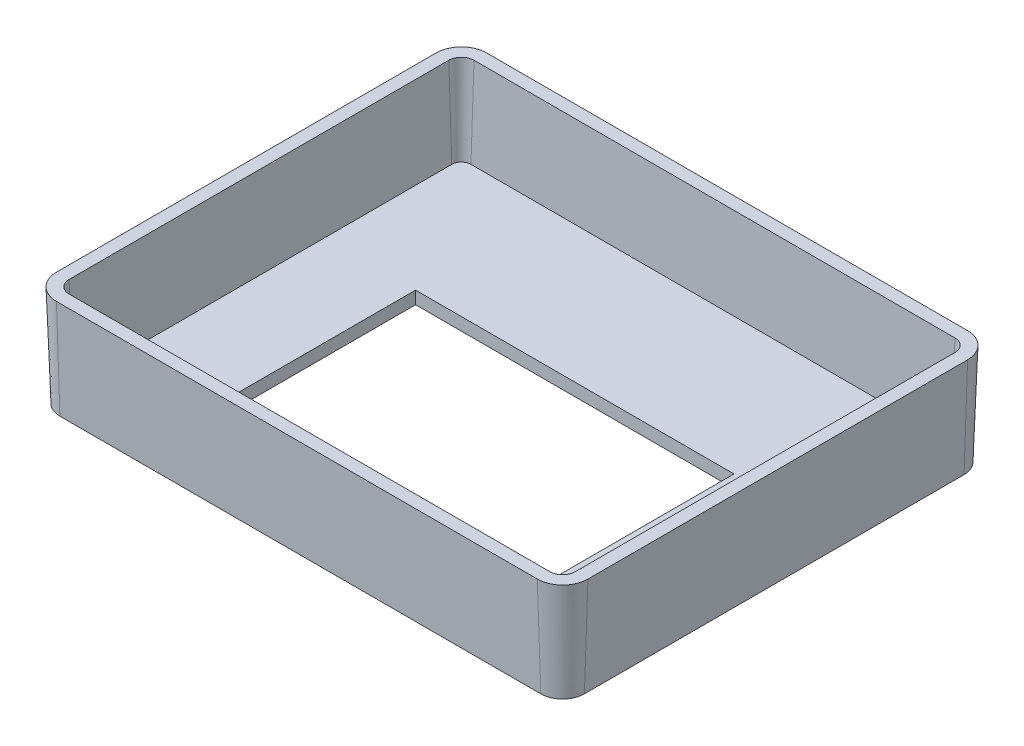
SolidWorks part; units mm, degrees
ref_plane "Front Plane" through (0, 0, 0) normal (0, 0, 1) x (1, 0, 0)
ref_plane "Top Plane" through (0, 0, 0) normal (0, 1, 0) x (1, 0, 0)
ref_plane "Right Plane" through (0, 0, 0) normal (1, 0, 0) x (0, 0, -1)
sketch "Sketch1" plane through (0, 0, 0) normal (0, 1, 0) x (1, 0, 0)
  line L1 (-9.5, -8.5) -> (9.5, -8.5)
  line L2 (-10.5, -7.5) -> (-10.5, 7.5)
  line L3 (-9.5, 8.5) -> (9.5, 8.5)
  line L4 (10.5, -7.5) -> (10.5, 7.5)
  line L5 (-10.5, -8.5) -> (10.5, 8.5) construction
  line L6 (-10.5, 8.5) -> (10.5, -8.5) construction
  arc A0 (-10.5, 7.5) -> (-9.5, 8.5) centre (-9.5, 7.5) cw
  arc A1 (10.5, 7.5) -> (9.5, 8.5) centre (9.5, 7.5) ccw
  arc A2 (10.5, -7.5) -> (9.5, -8.5) centre (9.5, -7.5) cw
  arc A3 (-9.5, -8.5) -> (-10.5, -7.5) centre (-9.5, -7.5) cw
  point P0 (0, 0)
  dimension "D3" = 1
  dimension "D1" = 21
  dimension "D2" = 17
extrude "Boss-Extrude1" add sketch "Sketch1" against normal blind 4 draft 2
shell "Shell1" thickness 0.5 removed face at (0, 0, 0)
sketch "Sketch2" plane through (0, -4, 0) normal (0, -1, 0) x (1, 0, 0)
  line L0 (-9.5, 8.5) -> (9.5, 8.5) construction
  line L1 (-6.29, 4.5) -> (6.29, 4.5)
  line L2 (-6.29, 4.5) -> (-6.29, -2.48)
  line L3 (-6.29, -2.48) -> (6.29, -2.48)
  line L4 (6.29, 4.5) -> (6.29, -2.48)
  point P0 (0, 0)
  dimension "D1" = 4
  dimension "D2" = 6.98
extrude "Cut-Extrude1" cut sketch "Sketch2" against normal blind 2
